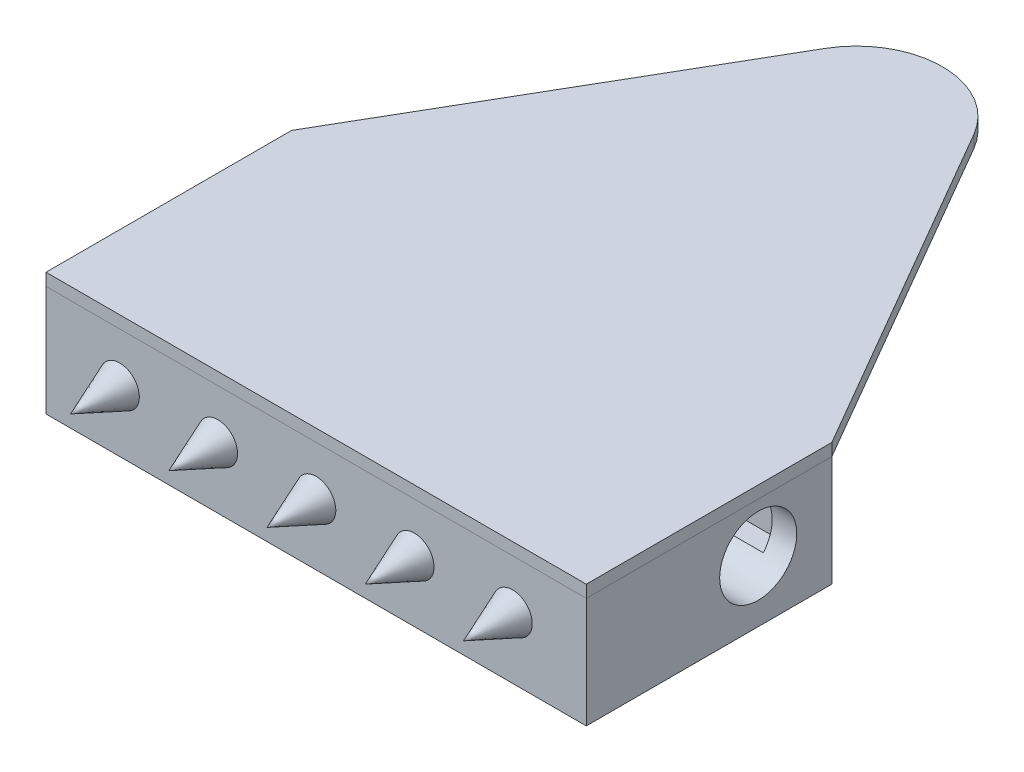
SolidWorks part; units mm, degrees
material "PLA/ABS"
ref_plane "Front Plane" through (0, 0, 0) normal (0, 0, 1) x (1, 0, 0)
ref_plane "Top Plane" through (0, 0, 0) normal (0, 1, 0) x (1, 0, 0)
ref_plane "Right Plane" through (0, 0, 0) normal (1, 0, 0) x (0, 0, -1)
other "Bounding Box"
ref_plane "Default Plane" through (-8.9266, -12.7485, 0) normal (-0.1736, 0.9848, 0) x (0.9848, 0.1736, 0)
sketch "Sketch1" plane through (0, 0, 0) normal (0, 1, 0) x (1, 0, 0)
  line L0 (0, 0) -> (0, -95.25) construction
  line L1 (0, -95.25) -> (-19.05, -95.25) construction
  line L2 (-76.2, -95.25) -> (-69.85, -95.25) construction
  line L3 (-69.85, -105.2195) -> (-19.05, -105.2195)
  line L4 (-69.85, -105.2195) -> (-69.85, -85.2805)
  line L5 (-69.85, -85.2805) -> (-19.05, -85.2805)
  line L6 (-19.05, -105.2195) -> (-19.05, -85.2805)
  line L7 (-69.85, -105.2195) -> (-19.05, -85.2805) construction
  line L8 (-69.85, -85.2805) -> (-19.05, -105.2195) construction
  line L9 (-88.9, -120.65) -> (-76.2, -120.65)
  line L10 (-88.9, -120.65) -> (-88.9, -69.85)
  line L11 (-88.9, -69.85) -> (-76.2, -69.85)
  line L12 (-76.2, -120.65) -> (-76.2, -69.85)
  line L13 (-88.9, -120.65) -> (-76.2, -69.85) construction
  line L14 (-88.9, -69.85) -> (-76.2, -120.65) construction
  line L15 (69.85, -85.2805) -> (19.05, -85.2805)
  line L16 (-63.5, -133.35) -> (-6.35, -133.35)
  line L17 (-63.5, -133.35) -> (-63.5, -116.84)
  line L18 (-63.5, -116.84) -> (-6.35, -116.84)
  line L19 (-6.35, -133.35) -> (-6.35, -116.84)
  line L20 (-63.5, -133.35) -> (-6.35, -116.84) construction
  line L21 (-63.5, -116.84) -> (-6.35, -133.35) construction
  line L22 (19.05, -105.2195) -> (19.05, -85.2805)
  line L23 (69.85, -105.2195) -> (19.05, -105.2195)
  line L24 (69.85, -105.2195) -> (69.85, -85.2805)
  line L25 (88.9, -69.85) -> (76.2, -69.85)
  line L26 (76.2, -120.65) -> (76.2, -69.85)
  line L27 (88.9, -120.65) -> (76.2, -120.65)
  line L28 (88.9, -120.65) -> (88.9, -69.85)
  line L30 (63.5, -133.35) -> (20.32, -133.35)
  line L31 (63.5, -133.35) -> (63.5, -113.2078)
  line L32 (63.5, -113.2078) -> (20.32, -113.2078)
  line L33 (20.32, -133.35) -> (20.32, -113.2078)
  line L34 (63.5, -133.35) -> (20.32, -113.2078) construction
  line L35 (63.5, -113.2078) -> (20.32, -133.35) construction
  line L36 (-69.85, -139.7) -> (69.85, -139.7)
  line L37 (-69.85, -139.7) -> (-69.85, -76.2)
  line L38 (-69.85, -76.2) -> (69.85, -76.2)
  line L39 (69.85, -139.7) -> (69.85, -76.2)
  line L40 (-69.85, -139.7) -> (69.85, -76.2) construction
  line L41 (-69.85, -76.2) -> (69.85, -139.7) construction
  circle A0 centre (0, 0) radius 69.85
  circle A1 centre (0, 0) radius 13.843
  point P3 (-34.925, -125.095)
  point P6 (-44.45, -95.25)
  point P12 (-82.55, -95.25)
  point P22 (0, -76.2)
  point P23 (0, -107.95)
  point P36 (0, -69.85)
  point P38 (41.91, -123.2789)
  dimension "D1" = 139.7
  dimension "D19" = 27.686
  dimension "D2" = 50.8
  dimension "D3" = 19.939
  dimension "D4" = 50.8
  dimension "D5" = 12.7
  dimension "D6" = 57.15
  dimension "D7" = 16.51
  dimension "D8" = 43.18
  dimension "D9" = 20.1422
  dimension "D10" = 6.35
  dimension "D11" = 139.7
  dimension "D12" = 44.45
  dimension "D13" = 6.35
  dimension "D14" = 6.35
  dimension "D15" = 6.35
  dimension "D16" = 6.35
  dimension "D17" = 63.5
  dimension "D18" = 6.35
sketch "Sketch2" plane through (0, 0, 0) normal (1, 0, 0) x (0, 0, -1)
  line L1 (-139.7, 12.7) -> (-76.2, 12.7)
  line L2 (-139.7, 12.7) -> (-139.7, -12.7)
  line L3 (-139.7, -12.7) -> (-76.2, -12.7)
  line L4 (-76.2, 12.7) -> (-76.2, -12.7)
  line L5 (-139.7, 12.7) -> (-76.2, -12.7) construction
  line L6 (-139.7, -12.7) -> (-76.2, 12.7) construction
  line L7 (-139.7, 12.7) -> (12.7, 12.7)
  line L8 (-139.7, 12.7) -> (-139.7, 15.875)
  line L9 (-139.7, 15.875) -> (12.7, 15.875)
  line L10 (12.7, 12.7) -> (12.7, 15.875)
  line L11 (-139.7, 12.7) -> (12.7, 15.875) construction
  line L12 (-139.7, 15.875) -> (12.7, 12.7) construction
  line L13 (-139.7, -12.7) -> (-76.2, -12.7)
  line L14 (-139.7, -12.7) -> (-139.7, -15.875)
  line L15 (-139.7, -15.875) -> (-76.2, -15.875)
  line L16 (-76.2, -12.7) -> (-76.2, -15.875)
  line L17 (-139.7, -12.7) -> (-76.2, -15.875) construction
  line L18 (-139.7, -15.875) -> (-76.2, -12.7) construction
  circle A0 centre (-95.25, 0) radius 25.4
  point P4 (-120.65, 0)
  point P5 (-107.95, 0)
  point P7 (13.7699, 14.2875)
  point P15 (-63.5, 14.2875)
  point P19 (-107.95, -14.2875)
  point P20 (0, 0)
  dimension "D1" = 25.4
  dimension "D2" = 3.175
  dimension "D3" = 12.7
sketch "Sketch3" plane through (0, 0, 0) normal (0, 1, 0) x (1, 0, 0)
  line L1 (-69.85, -139.7) -> (69.85, -139.7)
  line L2 (-69.85, -139.7) -> (-69.85, -76.2)
  line L3 (-69.85, -76.2) -> (69.85, -76.2)
  line L4 (69.85, -139.7) -> (69.85, -76.2)
  line L5 (-69.85, -139.7) -> (69.85, -76.2) construction
  line L6 (-69.85, -76.2) -> (69.85, -139.7) construction
  line L7 (-63.5, -82.55) -> (63.5, -82.55)
  line L8 (-63.5, -82.55) -> (-63.5, -133.35)
  line L9 (-63.5, -133.35) -> (63.5, -133.35)
  line L10 (63.5, -82.55) -> (63.5, -133.35)
  line L11 (-63.5, -82.55) -> (63.5, -133.35) construction
  line L12 (-63.5, -133.35) -> (63.5, -82.55) construction
  point P0 (0, -107.95)
  point P7 (0, -107.95)
  point P12 (-63.5, -146.05)
extrude "Boss-Extrude1" add sketch "Sketch3" along normal up to vertex (12.7 mm away) and the other way up to vertex (12.7 mm away) up to point (0, 12.7, 139.7) other way up to point (0, -12.7, 139.7)
sketch "Sketch4" plane through (0, -12.7, 0) normal (0, -1, 0) x (1, 0, 0)
  line L1 (-69.85, 139.7) -> (69.85, 139.7)
  line L2 (-69.85, 139.7) -> (-69.85, 76.2)
  line L3 (-69.85, 76.2) -> (69.85, 76.2)
  line L4 (69.85, 139.7) -> (69.85, 76.2)
  line L5 (-69.85, 139.7) -> (69.85, 76.2) construction
  line L6 (-69.85, 76.2) -> (69.85, 139.7) construction
  point P0 (0, 107.95)
extrude "Boss-Extrude2" add sketch "Sketch4" along normal up to vertex (3.175 mm away) up to point (0, -15.875, 139.7)
sketch "Sketch5" plane through (0, 12.7, 0) normal (0, 1, 0) x (1, 0, 0)
  line L0 (-19.229, 11.1443) -> (-69.85, -76.2)
  line L1 (-69.85, -76.2) -> (-69.85, -139.7)
  line L2 (-69.85, -139.7) -> (69.85, -139.7)
  line L3 (69.85, -139.7) -> (69.85, -76.2)
  line L4 (69.85, -76.2) -> (19.229, 11.1443)
  arc A0 (-19.229, 11.1443) -> (19.229, 11.1443) centre (0, 0) cw
  dimension "D1" = 22.225
extrude "Boss-Extrude3" add sketch "Sketch5" along normal up to vertex (3.175 mm away) separate body up to point (0, 15.875, 139.7)
sketch "Sketch7" plane through (0, -12.7, 0) normal (0, 1, 0) x (1, 0, 0)
  line L0 (-19.05, -105.2195) -> (-19.05, -85.2805) construction
  line L1 (-63.5, -82.55) -> (-19.05, -82.55)
  line L2 (-63.5, -82.55) -> (-63.5, -107.95)
  line L3 (-63.5, -107.95) -> (-19.05, -107.95)
  line L4 (-19.05, -82.55) -> (-19.05, -107.95)
  line L5 (-63.5, -82.55) -> (-19.05, -107.95) construction
  line L6 (-63.5, -107.95) -> (-19.05, -82.55) construction
  line L7 (63.5, -82.55) -> (19.05, -82.55)
  line L8 (63.5, -82.55) -> (63.5, -107.95)
  line L9 (63.5, -107.95) -> (19.05, -107.95)
  line L10 (19.05, -82.55) -> (19.05, -107.95)
  line L11 (63.5, -82.55) -> (19.05, -107.95) construction
  line L12 (63.5, -107.95) -> (19.05, -82.55) construction
  line L13 (19.05, -105.2195) -> (19.05, -85.2805) construction
  line L14 (0, -95.25) -> (-19.05, -95.25) construction
  point P4 (-41.275, -95.25)
  point P10 (41.275, -95.25)
  point P12 (28.5906, -110.7269)
  point P13 (-23.6056, -110.7269)
  point P18 (0, 0)
extrude "Boss-Extrude4" add sketch "Sketch7" along normal blind 6.35
sketch "Sketch6" plane through (-69.85, 0, 0) normal (-1, 0, 0) x (0, 0, 1)
  circle A0 centre (95.25, 0) radius 9.9695
  point P2 (0, 0)
extrude "Cut-Extrude1" cut sketch "Sketch6" against normal through all
ref_plane "Plane1" through (0, 0, 0) normal (1, 0, 0) x (0, 0, -1)
sketch "Sketch9" plane through (0, 0, 0) normal (1, 0, 0) x (0, 0, -1)
  line L0 (-139.7, 0) -> (-139.7, 5.08)
  line L1 (-139.7, 12.7) -> (-139.7, -15.875) construction
  line L2 (-139.7, 5.08) -> (-152.4, 0)
  line L3 (-152.4, 0) -> (-139.7, 0)
  point P6 (-139.7, 4.2671)
  dimension "D1" = 12.7
  dimension "D2" = 5.08
revolve "Revolve1" add sketch "Sketch9" angle 360 about L3
pattern_linear "LPattern1" count 3 spacing 25.4 along (-1, 0, 0) count 3 spacing 25.4 along (1, 0, 0) of "Revolve1"
